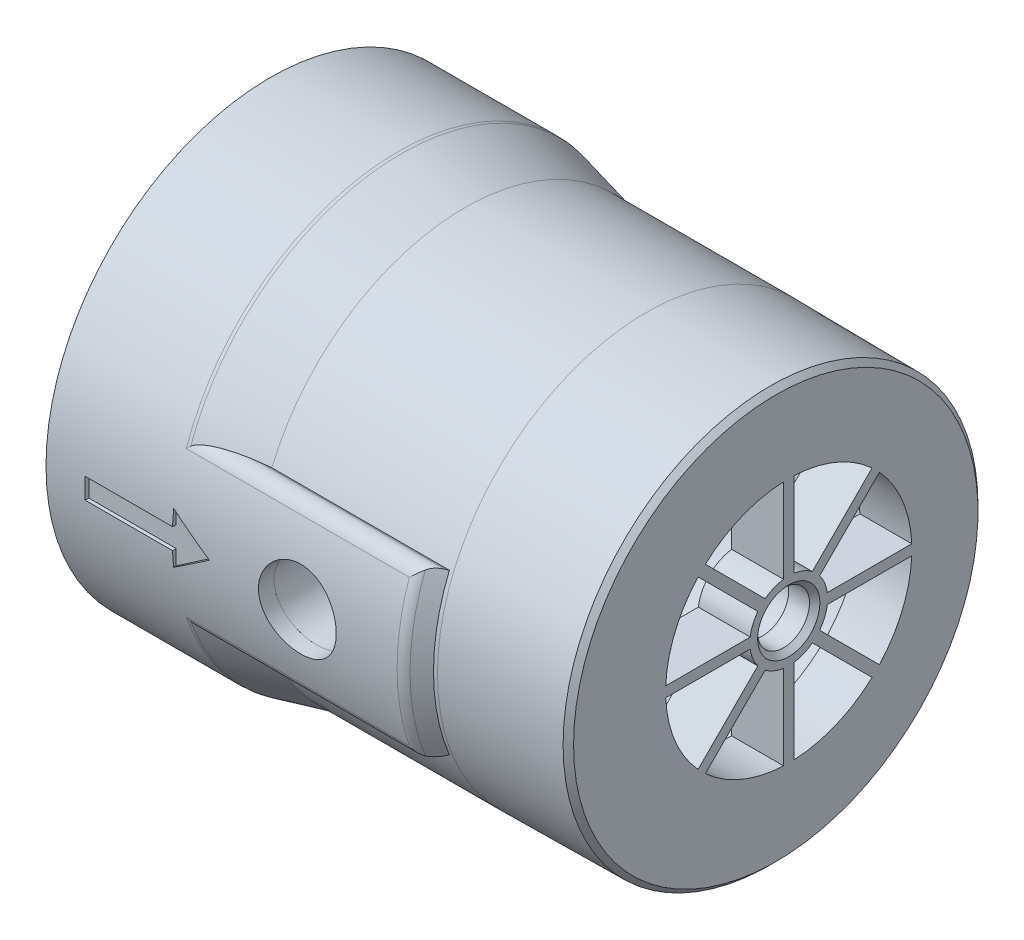
SolidWorks part; units mm, degrees
ref_plane "Front Plane" through (0, 0, 0) normal (0, 0, 1) x (1, 0, 0)
ref_plane "Top Plane" through (0, 0, 0) normal (0, 1, 0) x (1, 0, 0)
ref_plane "Right Plane" through (0, 0, 0) normal (1, 0, 0) x (0, 0, -1)
sketch "Sketch1" plane through (0, 0, 0) normal (0, 0, 1) x (1, 0, 0)
  line L0 (-80.1124, 0) -> (69.6237, 0) construction
  line L1 (-80.2087, 17.3) -> (-70.2087, 17.3)
  line L2 (-70.2087, 17.3) -> (-65.2087, 16.1)
  line L3 (-65.2087, 16.1) -> (-51.2087, 16.1)
  line L4 (-80.2087, 16.1) -> (-70.2092, 16.1)
  line L5 (-70.2092, 16.1) -> (-65.2092, 14.9)
  line L6 (-65.2092, 14.9) -> (-45.2092, 14.9)
  line L7 (-80.2087, 17.3) -> (-80.2087, 16.1)
  line L8 (-45.2092, 14.9) -> (-45.2092, 0)
  line L9 (-45.2092, 0) -> (-41.2092, 0)
  line L10 (-41.2092, 0) -> (-41.2092, 16)
  line L11 (-41.2092, 16) -> (-51.2087, 16.1)
  line L12 (-70.2087, 17.3) -> (-70.2092, 16.1) construction
  dimension "D2" = 10
  dimension "D3" = 16.1
  dimension "D4" = 10
  dimension "D5" = 14
  dimension "D6" = 5
  dimension "D7" = 16.1
  dimension "D8" = 41.2092
  dimension "D9" = 20
  dimension "D1" = 4
  dimension "D10" = 5
  dimension "D11" = 16
  dimension "D12" = 1.2
  dimension "D13" = 1.2
revolve "Revolve1" add sketch "Sketch1" angle 360 about L0
sketch "Sketch2" plane through (-41.2092, 0, 0) normal (1, 0, 0) x (0, 0, -1)
  line L0 (1, 0) -> (-21.0341, 0) construction
  line L1 (-8.4916, 0.4) -> (-3.482, 0.4)
  line L3 (1, 0) -> (-21.0341, 0) construction
  line L10 (1, 0) -> (-16.203, 17.203) construction
  line L11 (-1.3852, 1.8195) -> (-1.9187, 2.353)
  line L12 (-3.482, 0.4) -> (-1.9732, 0.4)
  line L13 (-1.9187, 2.353) -> (-5.9944, 6.4287)
  line L14 (0.6, 3.7276) -> (0.6, 9.4916)
  line L15 (-5.4287, 6.9944) -> (-1.8864, 3.4521)
  line L16 (0.6, 2.9732) -> (0.6, 3.7276)
  line L17 (-1.8864, 3.4521) -> (-0.8195, 2.3852)
  line L18 (3.353, 2.9187) -> (7.4287, 6.9944)
  line L19 (1.4, 9.4916) -> (1.4, 4.482)
  line L20 (2.8195, 2.3852) -> (3.353, 2.9187)
  line L21 (1.4, 4.482) -> (1.4, 2.9732)
  line L22 (4.7276, 0.4) -> (10.4916, 0.4)
  line L23 (7.9944, 6.4287) -> (4.4521, 2.8864)
  line L24 (3.9732, 0.4) -> (4.7276, 0.4)
  line L25 (4.4521, 2.8864) -> (3.3852, 1.8195)
  line L26 (3.9187, -2.353) -> (7.9944, -6.4287)
  line L27 (10.4916, -0.4) -> (5.482, -0.4)
  line L28 (3.3852, -1.8195) -> (3.9187, -2.353)
  line L29 (5.482, -0.4) -> (3.9732, -0.4)
  line L30 (1.4, -3.7276) -> (1.4, -9.4916)
  line L31 (7.4287, -6.9944) -> (3.8864, -3.4521)
  line L32 (1.4, -2.9732) -> (1.4, -3.7276)
  line L33 (3.8864, -3.4521) -> (2.8195, -2.3852)
  line L34 (-1.353, -2.9187) -> (-5.4287, -6.9944)
  line L35 (0.6, -9.4916) -> (0.6, -4.482)
  line L36 (-0.8195, -2.3852) -> (-1.353, -2.9187)
  line L37 (0.6, -4.482) -> (0.6, -2.9732)
  line L38 (-2.7276, -0.4) -> (-8.4916, -0.4)
  line L39 (-5.9944, -6.4287) -> (-2.4521, -2.8864)
  line L40 (-1.9732, -0.4) -> (-2.7276, -0.4)
  line L41 (-2.4521, -2.8864) -> (-1.3852, -1.8195)
  circle A9 centre (0, 0) radius 16 construction
  arc A11 (-1.9732, 0.4) -> (-1.3852, 1.8195) centre (1, 0) cw
  arc A15 (-8.4916, 0.4) -> (-5.9944, 6.4287) centre (1, 0) cw
  arc A18 (-5.4287, 6.9944) -> (0.6, 9.4916) centre (1, 0) cw
  arc A21 (-0.8195, 2.3852) -> (0.6, 2.9732) centre (1, 0) cw
  arc A22 (1.4, 9.4916) -> (7.4287, 6.9944) centre (1, 0) cw
  arc A25 (1.4, 2.9732) -> (2.8195, 2.3852) centre (1, 0) cw
  arc A26 (7.9944, 6.4287) -> (10.4916, 0.4) centre (1, 0) cw
  arc A29 (3.3852, 1.8195) -> (3.9732, 0.4) centre (1, 0) cw
  arc A30 (10.4916, -0.4) -> (7.9944, -6.4287) centre (1, 0) cw
  arc A33 (3.9732, -0.4) -> (3.3852, -1.8195) centre (1, 0) cw
  arc A34 (7.4287, -6.9944) -> (1.4, -9.4916) centre (1, 0) cw
  arc A37 (2.8195, -2.3852) -> (1.4, -2.9732) centre (1, 0) cw
  arc A38 (0.6, -9.4916) -> (-5.4287, -6.9944) centre (1, 0) cw
  arc A41 (0.6, -2.9732) -> (-0.8195, -2.3852) centre (1, 0) cw
  arc A42 (-5.9944, -6.4287) -> (-8.4916, -0.4) centre (1, 0) cw
  arc A45 (-1.3852, -1.8195) -> (-1.9732, -0.4) centre (1, 0) cw
  point P11 (1, 0)
  point P27 (2, 0)
  point P74 (1, 0)
  dimension "D2" = 0.4
  dimension "D4" = 3
  dimension "D8" = 9.5
  dimension "D9" = 8
  dimension "D1" = 45
  dimension "D3" = 0.4
  dimension "D5" = 1
ref_plane "Plane1" through (0, 0, 12) normal (0, 0, 1) x (1, 0, 0)
extrude "Cut-Extrude5" cut sketch "Sketch2" against normal up to next
ref_plane "Plane3" through (0, 0, -1) normal (0, 0, -1) x (-1, 0, 0)
sketch "Sketch8" plane through (0, 0, -1) normal (0, 0, -1) x (-1, 0, 0)
  line L0 (41.4715, 0) -> (64.2594, 0) construction
  line L1 (45.2092, -2.5) -> (43.2092, -2.5)
  line L2 (41.2092, 16) -> (41.2092, -16) construction
  line L3 (45.2092, -2.5) -> (45.2092, 0)
  line L4 (41.2092, -2) -> (41.2092, 0)
  line L5 (45.2092, 0) -> (41.2092, 0)
  line L6 (43.2092, -2.5) -> (43.2092, -2)
  line L7 (43.2092, -2) -> (41.2092, -2)
  dimension "D1" = 2.5
  dimension "D2" = 2
  dimension "D3" = 4
  dimension "D4" = 2
revolve "Cut-Revolve2" cut sketch "Sketch8" angle 360 about L0
chamfer "Chamfer1" distance 0.4 angle 45 3 edges at (-41.2092, 0, 16) (-80.2087, 0, 16.1) (-41.2092, 0, -3) first distance on face at (-41.2092, 0, -3) first distance on face at (-80.2087, 0, 16.1)
fillet "Fillet4" radius 10 1 edges at (-70.2092, 0, 16.1)
sketch "Sketch12" plane through (0, 0, 0) normal (0, 1, 0) x (1, 0, 0)
  line L0 (-38.7859, 0) -> (-87.7556, 0) construction
  line L1 (-51.5117, -16.103) -> (-65.2087, -16.1)
  line L3 (-70.2087, -17.3) -> (-52.7087, -17.3)
  line L4 (-70.2092, 17.2) -> (-65.2092, 16)
  line L5 (-65.2087, -16.1) -> (-70.2087, -17.3)
  line L6 (-65.2087, -16.1) -> (-70.2087, -17.3)
  line L7 (-52.7087, -17.3) -> (-51.5117, -16.103)
  line L8 (-65.2092, 16) -> (-41.2092, 16)
  line L9 (-41.6132, -16.004) -> (-51.2087, -16.1)
  line L10 (-41.6132, -16.004) -> (-51.2087, -16.1) construction
  dimension "D1" = 17.5
  dimension "D2" = 45
revolve "Revolve2" add sketch "Sketch12" angle 45 mid plane about L0 region at (-59.976, 0, 16.7251)
ref_plane "Plane4" through (0, 0, 17) normal (0, 0, 1) x (1, 0, 0)
sketch "Sketch13" plane through (0, 0, 17) normal (0, 0, 1) x (1, 0, 0)
  line L0 (-77.1995, 0.799) -> (-70.4645, 0.799)
  line L1 (-70.4645, 1.958) -> (-70.4645, 0.799)
  line L2 (-70.4645, 1.958) -> (-67.6061, 0)
  line L3 (-77.1995, 0.799) -> (-77.1995, -0.799)
  line L4 (-66.0568, 0) -> (-78.8911, 0) construction
  line L5 (-77.1995, -0.799) -> (-70.4645, -0.799)
  line L6 (-70.4645, -1.958) -> (-70.4645, -0.799)
  line L7 (-70.4645, -1.958) -> (-67.6061, 0)
  point P10 (-77.1995, 0)
extrude "Cut-Extrude6" cut sketch "Sketch13" along normal blind 1.2
fillet "Fillet7" radius 1 4 edges at (-61.4587, 6.6204, 15.9831) (-52.7087, 0, 17.3) (-61.4587, -6.6204, 15.9831) (-70.2087, 0, -17.3)
sketch "Sketch3" plane through (0, 0, 12) normal (0, 0, 1) x (1, 0, 0)
  line L6 (-65.8174, 16.2461) -> (-65.8174, -16.2461) construction
  line L7 (-65.8174, 10.2323) -> (-41.2092, 10.2323)
  line L8 (-65.8174, 10.2323) -> (-65.8174, -10.138)
  line L9 (-65.8174, -10.138) -> (-41.2092, -10.138)
  line L10 (-41.2092, 10.2323) -> (-41.2092, -10.138)
  line L11 (-41.2092, -16) -> (-41.2092, 16) construction
extrude "Boss-Extrude1" add sketch "Sketch3" along normal up to body separate body
sketch "Sketch4" plane through (0, 0, 12) normal (0, 0, 1) x (1, 0, 0)
  line L0 (-65.8174, 16.2461) -> (-65.8174, -16.2461) construction
  line L2 (-71.1934, 0) -> (-58.0618, 0) construction
  circle A0 centre (-60.8174, 0) radius 2
  dimension "D2" = 4
  dimension "D1" = 5
extrude "Cut-Extrude2" cut sketch "Sketch4" along normal up to next
ref_plane "Plane2" through (0, 0, 12.8) normal (0, 0, 1) x (1, 0, 0)
sketch "Sketch5" plane through (0, 0, 12.8) normal (0, 0, 1) x (1, 0, 0)
  circle A0 centre (-60.8174, 0) radius 3
  dimension "D1" = 6
extrude "Cut-Extrude4" cut sketch "Sketch5" along normal through all
fillet "Fillet2" radius 2 2 edges at (-55.2092, 8.8323, 12) (-55.2092, -8.8323, 12)
fillet "Fillet9" radius 1 1 edges at (-65.8174, 0, 12)
fillet "Fillet12" radius 0.4 4 edges at (-45.2092, 8.8198, 11.8842) (-45.2092, 0, 12) (-45.2092, -8.8198, 11.8842) (-45.2092, 0, -14.9)
